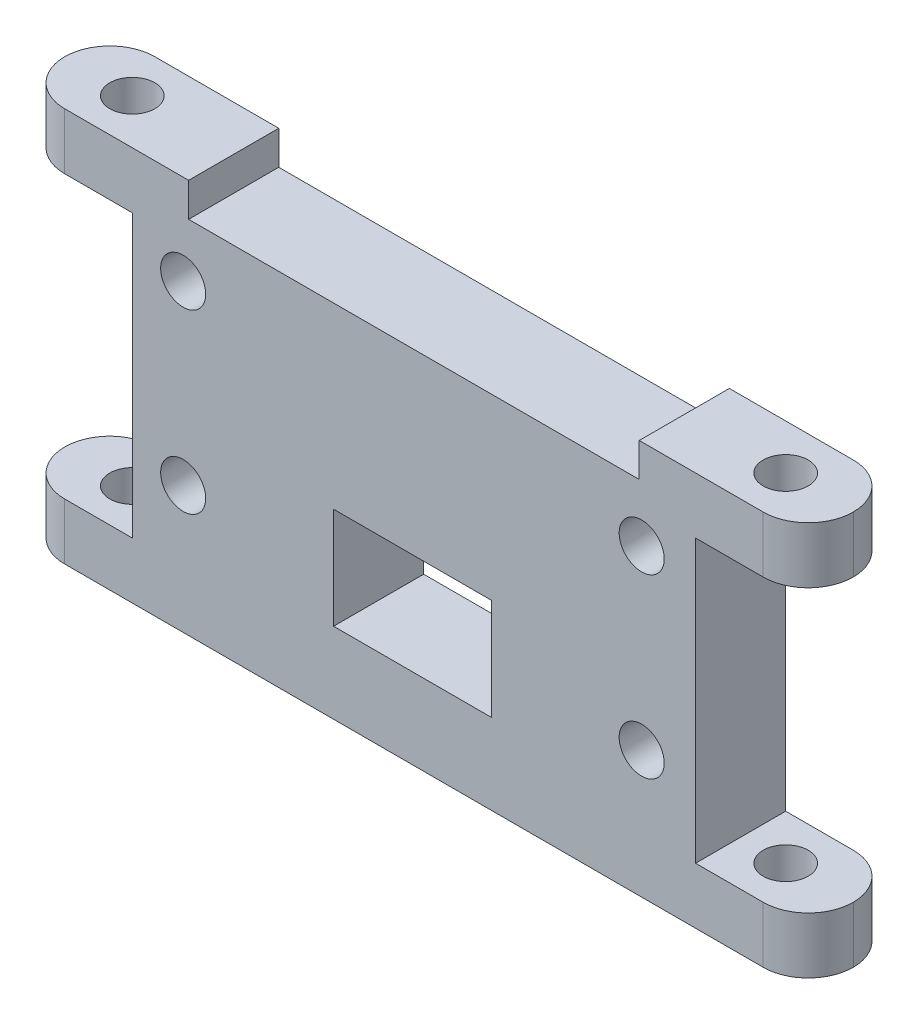
SolidWorks part; units mm, degrees
ref_plane "Front Plane" through (0, 0, 0) normal (0, 0, 1) x (1, 0, 0)
ref_plane "Top Plane" through (0, 0, 0) normal (0, 1, 0) x (1, 0, 0)
ref_plane "Right Plane" through (0, 0, 0) normal (1, 0, 0) x (0, 0, -1)
sketch "Sketch1" plane through (0, 0, 0) normal (0, 0, 1) x (1, 0, 0)
  line L1 (-25.7207, 19.4872) -> (44.2793, 19.4872)
  line L2 (-25.7207, 19.4872) -> (-25.7207, -15.5128)
  line L3 (-25.7207, -15.5128) -> (44.2793, -15.5128)
  line L4 (44.2793, 19.4872) -> (44.2793, -15.5128)
  dimension "D1" = 35
  dimension "D2" = 70
extrude "Boss-Extrude1" add sketch "Sketch1" along normal blind 8
fillet "Fillet3" radius 4 4 edges at (44.2793, 1.9872, 0) (44.2793, 1.9872, 8) (-25.7207, 1.9872, 0) (-25.7207, 1.9872, 8)
sketch "Sketch7" plane through (0, -15.5128, 0) normal (0, -1, 0) x (1, 0, 0)
  line L0 (-21.7207, 8) -> (40.2793, 8) construction
  line L1 (-21.7207, 0) -> (40.2793, 0) construction
  circle A0 centre (38.2793, 4) radius 2
  circle A1 centre (-19.7207, 4) radius 2
  dimension "D1" = 4
  dimension "D2" = 4
  dimension "D4" = 4
  dimension "D5" = 6
  dimension "D6" = 4
  dimension "D3" = 6
extrude "Cut-Extrude4" cut sketch "Sketch7" against normal blind 35
sketch "Sketch8" plane through (0, 0, 0) normal (0, 0, -1) x (-1, 0, 0)
  line L0 (-3.1443, -7.3628) -> (-15.1443, -7.3628) construction
  line L1 (-2.1443, -8.3628) -> (-16.1443, -8.3628)
  line L2 (-2.1443, -8.3628) -> (-2.1443, 0.6372)
  line L3 (-2.1443, 0.6372) -> (-16.1443, 0.6372)
  line L4 (-16.1443, -8.3628) -> (-16.1443, 0.6372)
  line L5 (-15.1443, -0.3628) -> (-3.1443, -0.3628) construction
  line L6 (-3.1443, -0.3628) -> (-3.1443, -7.3628) construction
  line L7 (-15.1443, -7.3628) -> (-15.1443, -0.3628) construction
  line L8 (21.7207, -15.5128) -> (21.7207, 19.4872) construction
  line L9 (-40.2793, 19.4872) -> (21.7207, 19.4872) construction
  circle A0 centre (-29.4943, -4.2128) radius 2
  circle A1 centre (-29.4943, 11.4872) radius 2
  circle A2 centre (11.2057, 11.4872) radius 2
  circle A3 centre (11.2057, -4.2128) radius 2
  dimension "D5" = 4
  dimension "D6" = 4
  dimension "D7" = 4
  dimension "D8" = 4
  dimension "D9" = 15.7
  dimension "D10" = 40.7
  dimension "D11" = 10.515
  dimension "D12" = 8
  dimension "D13" = 8
  dimension "D14" = 15.7
  dimension "D15" = 40.7
  dimension "D16" = 10.515
  dimension "D1" = 1
  dimension "D2" = 1
  dimension "D3" = 1
  dimension "D4" = 1
extrude "Cut-Extrude5" cut sketch "Sketch8" against normal through all
sketch "Sketch10" plane through (0, 19.4872, 0) normal (0, 1, 0) x (1, 0, 0)
  line L0 (40.2793, 0) -> (-21.7207, 0) construction
  line L1 (29.2793, 0) -> (-10.7207, 0)
  line L2 (29.2793, 0) -> (29.2793, -8)
  line L3 (29.2793, -8) -> (-10.7207, -8)
  line L4 (-10.7207, 0) -> (-10.7207, -8)
  line L5 (40.2793, -8) -> (-21.7207, -8) construction
  dimension "D1" = 40
  dimension "D2" = 15
extrude "Cut-Extrude6" cut sketch "Sketch10" against normal blind 3
sketch "Sketch12" plane through (0, 0, 0) normal (0, 0, -1) x (-1, 0, 0)
  line L0 (25.7207, -15.5128) -> (25.7207, 19.4872) construction
  line L1 (15.7207, 14.4872) -> (25.7207, 14.4872)
  line L2 (15.7207, 14.4872) -> (15.7207, -10.5128)
  line L3 (15.7207, -10.5128) -> (25.7207, -10.5128)
  line L4 (25.7207, 14.4872) -> (25.7207, -10.5128)
  line L5 (10.7207, 19.4872) -> (21.7207, 19.4872) construction
  line L6 (21.7207, -15.5128) -> (-40.2793, -15.5128) construction
  line L8 (-44.2793, 19.4872) -> (-44.2793, -15.5128) construction
  line L9 (-34.2793, 14.4872) -> (-44.2793, 14.4872)
  line L10 (-34.2793, 14.4872) -> (-34.2793, -10.5128)
  line L11 (-34.2793, -10.5128) -> (-44.2793, -10.5128)
  line L12 (-44.2793, 14.4872) -> (-44.2793, -10.5128)
  line L13 (-40.2793, 19.4872) -> (-29.2793, 19.4872) construction
  dimension "D1" = 5
  dimension "D2" = 5
  dimension "D3" = 10
  dimension "D4" = 5
  dimension "D5" = 10
  dimension "D6" = 5
extrude "Cut-Extrude7" cut sketch "Sketch12" against normal through all
